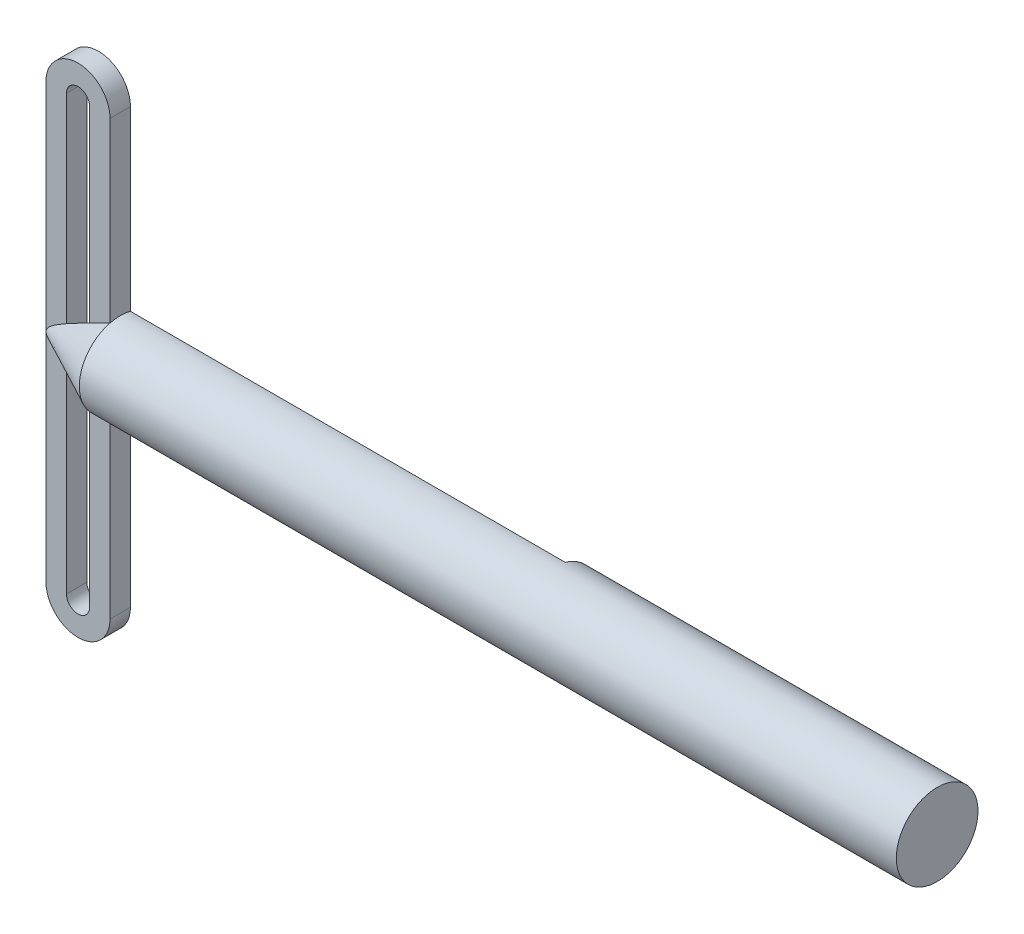
SolidWorks part; units mm, degrees
ref_plane "Front Plane" through (0, 0, 0) normal (0, 0, 1) x (1, 0, 0)
ref_plane "Top Plane" through (0, 0, 0) normal (0, 1, 0) x (1, 0, 0)
ref_plane "Right Plane" through (0, 0, 0) normal (1, 0, 0) x (0, 0, -1)
sketch "Sketch1" plane through (0, 0, 0) normal (0, 0, 1) x (1, 0, 0)
  line L0 (0, 67.4002) -> (0, -67.4002) construction
  line L1 (3.6016, 67.4002) -> (3.6016, -67.4002)
  line L2 (-3.6016, 67.4002) -> (-3.6016, -67.4002)
  line L3 (9.9516, 67.4002) -> (9.9516, -67.4002)
  line L4 (-9.9516, 67.4002) -> (-9.9516, -67.4002)
  arc A0 (3.6016, 67.4002) -> (-3.6016, 67.4002) centre (0, 67.4002) ccw
  arc A1 (-3.6016, -67.4002) -> (3.6016, -67.4002) centre (0, -67.4002) ccw
  arc A2 (-9.9516, -67.4002) -> (9.9516, -67.4002) centre (0, -67.4002) ccw
  arc A3 (9.9516, 67.4002) -> (-9.9516, 67.4002) centre (0, 67.4002) ccw
  point P2 (0, 0)
  dimension "D2" = 3.6016
  dimension "D1" = 134.8003
  dimension "D3" = 6.35
extrude "Boss-Extrude1" add sketch "Sketch1" along normal mid plane 6.35
sketch "Sketch2" plane through (9.9516, 0, 0) normal (1, 0, 0) x (0, 0, -1)
  circle A0 centre (0, 0) radius 12.7
extrude "Boss-Extrude2" add sketch "Sketch2" along normal blind 254
sketch "Sketch5" plane through (9.9516, 0, 0) normal (-1, 0, 0) x (0, 0, 1)
  line L0 (-3.175, -12.2967) -> (-3.175, 12.2967) construction
  line L1 (3.175, 12.2967) -> (3.175, -12.2967) construction
  line L2 (-3.175, -12.2967) -> (-3.175, 12.2967)
  line L3 (3.175, 12.2967) -> (3.175, -12.2967)
  arc A0 (-3.175, 12.2967) -> (-3.175, -12.2967) centre (0, 0) ccw construction
  arc A1 (3.175, -12.2967) -> (3.175, 12.2967) centre (0, 0) ccw construction
  arc A2 (-3.175, 12.2967) -> (-3.175, -12.2967) centre (0, 0) ccw
  arc A3 (3.175, -12.2967) -> (3.175, 12.2967) centre (0, 0) ccw
extrude "Boss-Extrude3" add sketch "Sketch5" along normal up to surface (19.9033 mm away) contours A2 L2 | L3 A3 up to face at (-9.9516, 0, 0)
sketch "Sketch15" plane through (-9.9516, 0, 0) normal (-1, 0, 0) x (0, 0, 1)
  line L0 (-3.175, 0) -> (-3.175, 155.575)
  line L1 (-3.175, 0) -> (-12.7, 0)
  line L2 (-12.7, 0) -> (-12.7, 155.575)
  line L3 (-12.7, 155.575) -> (-3.175, 155.575)
  point P3 (0, 0)
  dimension "D1" = 155.575
  dimension "D2" = 9.525
revolve "Cut-Revolve2" cut sketch "Sketch15" angle 360 about L1
chamfer "Chamfer1" distance 9.525 angle 64.4 1 edges at (-9.9516, 0, 12.7) first distance on face at (-9.9516, 0, 2.6458)
